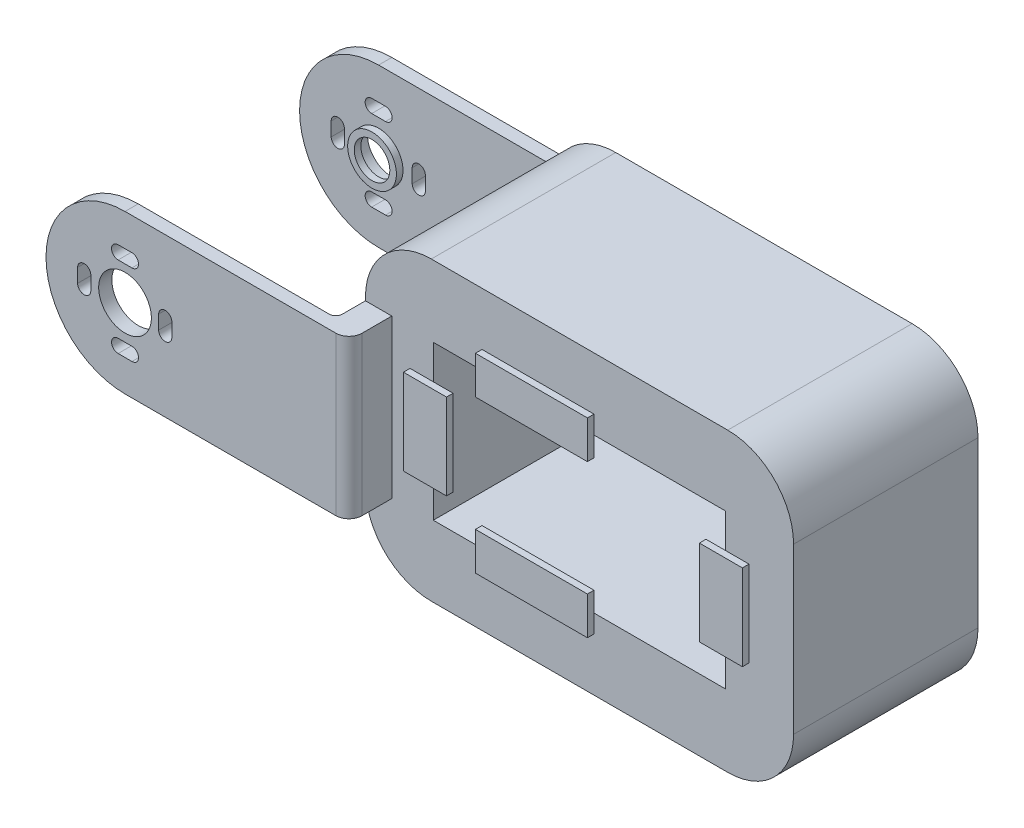
SolidWorks part; units mm, degrees
ref_plane "前基準面" through (0, 0, 0) normal (0, 0, 1) x (1, 0, 0)
ref_plane "上基準面" through (0, 0, 0) normal (0, 1, 0) x (1, 0, 0)
ref_plane "右基準面" through (0, 0, 0) normal (1, 0, 0) x (0, 0, -1)
sketch "草圖1" plane through (0, 0, 0) normal (0, 0, 1) x (1, 0, 0)
  line L0 (-9.02, 0) -> (7.9922, 0) construction
  line L2 (-59.9347, 22.5) -> (5.0653, 22.5)
  line L3 (-59.9347, 22.5) -> (-59.9347, -22.5)
  line L4 (-59.9347, -22.5) -> (5.0653, -22.5)
  line L5 (5.0653, 22.5) -> (5.0653, -22.5)
  dimension "D1" = 45
  dimension "D2" = 22.5
  dimension "D3" = 65
extrude "填料-伸長1" add sketch "草圖1" along normal blind 28
sketch "草圖2" plane through (0, 0, 0) normal (0, 0, 1) x (1, 0, 0)
  line L0 (-59.9347, 0) -> (5.361, 0) construction
  line L1 (-59.9347, 22.5) -> (-59.9347, -22.5) construction
  line L2 (-27.4347, 22.5) -> (-27.4347, -22.5) construction
  line L3 (5.0653, 22.5) -> (-59.9347, 22.5) construction
  line L4 (-59.9347, -22.5) -> (5.0653, -22.5) construction
  line L6 (-49.6347, 11.7) -> (-5.2347, 11.7)
  line L7 (-49.6347, 11.7) -> (-49.6347, -11.7)
  line L8 (-49.6347, -11.7) -> (-5.2347, -11.7)
  line L9 (-5.2347, 11.7) -> (-5.2347, -11.7)
  dimension "D1" = 44.4
  dimension "D2" = 23.4
  dimension "D3" = 10.3
  dimension "D4" = 10.8
extrude "除料-伸長1" cut sketch "草圖2" along normal blind 39
ref_plane "平面1" through (0, 0, 28) normal (0, 0, 1) x (1, 0, 0)
sketch "草圖3" plane through (0, 0, 28) normal (0, 0, 1) x (1, 0, 0)
  line L0 (-59.9347, 22.5) -> (-59.9347, -22.5) construction
  line L2 (-59.9347, 12) -> (-55.9347, 12)
  line L3 (-59.9347, 12) -> (-59.9347, -12)
  line L4 (-59.9347, -12) -> (-55.9347, -12)
  line L5 (-55.9347, 12) -> (-55.9347, -12)
  line L8 (-5.2347, -11.7) -> (-49.6347, -11.7) construction
  dimension "D1" = 4
  dimension "D2" = 24
  dimension "D3" = 0.3
extrude "填料-伸長2" add sketch "草圖3" along normal blind 6
ref_plane "平面2" through (-59.9347, 0, 0) normal (-1, 0, 0) x (0, 0, 1)
sketch "草圖4" plane through (-59.9347, 0, 0) normal (-1, 0, 0) x (0, 0, 1)
  line L0 (34, 12) -> (28, 12) construction
  line L2 (32, 12) -> (34, 12)
  line L3 (32, 12) -> (32, -12)
  line L4 (32, -12) -> (34, -12)
  line L5 (34, 12) -> (34, -12)
  dimension "D1" = 2
ref_plane "平面3" through (0, 0, 33) normal (0, 0, 1) x (1, 0, 0)
sketch "草圖6" plane through (0, 0, 28) normal (0, 0, 1) x (1, 0, 0)
  line L0 (-15.2347, 0.3) -> (5.0653, -22.5)
  line L1 (-5.2347, 11.7) -> (-5.2347, -11.7) construction
  line L2 (-5.2347, -11.7) -> (-49.6347, -11.7) construction
  line L3 (-15.2347, 0.3) -> (-15.2347, -22.5)
  line L4 (-59.9347, -22.5) -> (5.0653, -22.5) construction
  line L5 (-15.2347, -22.5) -> (5.0653, -22.5)
  dimension "D1" = 10
  dimension "D2" = 12
sketch "草圖7" plane through (0, 0, 33) normal (0, 0, 1) x (1, 0, 0)
  line L1 (-59.9347, 12) -> (-59.9347, -12) construction
  line L3 (-59.9347, 0) -> (-109.9347, 0) construction
  line L5 (-96.1347, 1.05) -> (-96.1347, -1.05) construction
  line L6 (-95.1347, 1.05) -> (-95.1347, -1.05)
  line L7 (-97.1347, 1.05) -> (-97.1347, -1.05)
  line L8 (-90.9847, -6.2) -> (-88.8847, -6.2) construction
  line L9 (-90.9847, -5.2) -> (-88.8847, -5.2)
  line L10 (-90.9847, -7.2) -> (-88.8847, -7.2)
  line L11 (-89.9347, 4) -> (-89.9347, -7.9506) construction
  line L12 (-90.9847, 6.1) -> (-88.8847, 6.1) construction
  line L13 (-90.9847, 5.1) -> (-88.8847, 5.1)
  line L14 (-90.9847, 7.1) -> (-88.8847, 7.1)
  line L15 (-83.8347, 1.05) -> (-83.8347, -1.05) construction
  line L16 (-84.8347, 1.05) -> (-84.8347, -1.05)
  line L17 (-82.8347, 1.05) -> (-82.8347, -1.05)
  line L19 (-59.9347, 12) -> (-59.9347, -12)
  line L20 (-59.9347, -12) -> (-89.9347, -12)
  line L21 (-59.9347, 12) -> (-89.9347, 12)
  circle A1 centre (-89.9347, 0) radius 4
  arc A3 (-95.1347, 1.05) -> (-97.1347, 1.05) centre (-96.1347, 1.05) ccw
  arc A4 (-97.1347, -1.05) -> (-95.1347, -1.05) centre (-96.1347, -1.05) ccw
  arc A5 (-90.9847, -5.2) -> (-90.9847, -7.2) centre (-90.9847, -6.2) ccw
  arc A6 (-88.8847, -7.2) -> (-88.8847, -5.2) centre (-88.8847, -6.2) ccw
  arc A7 (-90.9847, 5.1) -> (-90.9847, 7.1) centre (-90.9847, 6.1) cw
  arc A8 (-88.8847, 7.1) -> (-88.8847, 5.1) centre (-88.8847, 6.1) cw
  arc A9 (-84.8347, 1.05) -> (-82.8347, 1.05) centre (-83.8347, 1.05) cw
  arc A10 (-82.8347, -1.05) -> (-84.8347, -1.05) centre (-83.8347, -1.05) cw
  arc A11 (-89.9347, 12) -> (-89.9347, -12) centre (-89.9347, 0) ccw
  point P15 (-96.1347, 0)
  point P20 (-89.9347, -6.2)
  point P31 (-89.9347, 6.1)
  point P38 (-83.8347, 0)
  dimension "D2" = 8
  dimension "D3" = 50
  dimension "D4" = 6.2
  dimension "D6" = 0
  dimension "D12" = 24
  dimension "D5" = 2.1
  dimension "D7" = 2
  dimension "D8" = 2
  dimension "D9" = 0
  dimension "D10" = 2.1
  dimension "D11" = 6.2
  dimension "D13" = 30
extrude "填料-伸長3" add sketch "草圖7" along normal blind 1.5 and the other way blind 0.5
ref_plane "平面4" through (0, 0, 0) normal (0, 0, -1) x (-1, 0, 0)
sketch "草圖8" plane through (0, 0, 0) normal (0, 0, -1) x (-1, 0, 0)
  line L0 (59.9347, 12) -> (59.9347, -12) construction
  line L1 (55.9347, 12) -> (59.9347, 12)
  line L2 (55.9347, 12) -> (55.9347, -12)
  line L3 (55.9347, -12) -> (59.9347, -12)
  line L4 (59.9347, 12) -> (59.9347, -12)
  dimension "D1" = 24
  dimension "D2" = 4
extrude "填料-伸長4" add sketch "草圖8" along normal blind 6 contours L3 L4 L1 L2
fillet "圓角1" radius 10 1 edges at (-59.9347, -22.5, 14) type face fillet first side face at (-59.9347, 0, 13.75) second side face at (-27.4347, -22.5, 14)
fillet "圓角2" radius 10 1 edges at (-59.9347, 22.5, 14) type face fillet first side face at (-27.4347, 22.5, 14) second side face at (-59.9347, 1.6667, 13.75)
fillet "圓角3" radius 10 1 edges at (5.0653, 22.5, 14) type face fillet first side face at (-22.4347, 22.5, 14) second side face at (5.0653, 0, 14)
fillet "圓角4" radius 10 1 edges at (5.0653, -22.5, 14) type face fillet first side face at (-22.4347, -22.5, 14) second side face at (5.0653, -5, 14)
pattern_linear "直線複製排列2" count 2 spacing 38.5 along (0, 0, -1) of "填料-伸長3"
fillet "圓角5" radius 2 1 edges at (-55.9347, 0, -6) type face fillet first side face at (-75.9347, 0, -6) second side face at (-55.9347, 0, -3)
ref_plane "平面5" through (0, 0, -4) normal (0, 0, 1) x (1, 0, 0)
sketch "草圖9" plane through (0, 0, -4) normal (0, 0, 1) x (1, 0, 0)
  circle A0 centre (-89.9347, 0) radius 3.7
  circle A1 centre (-89.9347, 0) radius 2.7
  dimension "D1" = 7.4
  dimension "D2" = 5.4
extrude "填料-伸長5" add sketch "草圖9" along normal blind 1 separate body
ref_plane "平面6" through (0, 0, 29) normal (0, 0, 1) x (1, 0, 0)
sketch "草圖10" plane through (0, 0, 29) normal (0, 0, 1) x (1, 0, 0)
  line L6 (-49.6347, 0) -> (-4.2092, 0) construction
  line L7 (-49.6347, -11.7) -> (-49.6347, 11.7) construction
  line L8 (-27.4347, -11.7) -> (-27.4347, 19.297) construction
  line L9 (-5.2347, -11.7) -> (-49.6347, -11.7) construction
  line L11 (-49.6347, 6.5) -> (-53.1651, 6.5)
  line L14 (-53.1651, 6.5) -> (-53.1651, -6.5)
  line L17 (-49.6347, 6.5) -> (-46.6347, 6.5)
  line L18 (-46.6347, 6.5) -> (-46.6347, -6.5)
  line L20 (-42.2347, -11.7) -> (-42.2347, -8.7)
  line L25 (-42.2347, -11.7) -> (-42.2347, -14.4546)
  line L27 (-8.2347, 6.5) -> (-8.2347, -6.5)
  line L28 (-8.2347, -6.5) -> (-5.2347, -6.5)
  line L29 (-5.2347, -6.5) -> (-1.7043, -6.5)
  line L30 (-1.7043, 6.5) -> (-1.7043, -6.5)
  line L32 (-25.2347, 8.7) -> (-25.2347, 14.4546)
  line L33 (-25.2347, -14.4546) -> (-25.2347, -8.7)
  line L34 (-25.2347, -14.4546) -> (-42.2347, -14.4546)
  line L35 (-25.2347, -8.7) -> (-42.2347, -8.7)
  line L36 (-25.2347, 8.7) -> (-42.2347, 8.7)
  line L37 (-25.2347, 14.4546) -> (-42.2347, 14.4546)
  line L38 (-42.2347, 8.7) -> (-42.2347, 14.4546)
  line L39 (-46.6347, -6.5) -> (-53.1651, -6.5)
  line L40 (-1.7043, 6.5) -> (-8.2347, 6.5)
  dimension "D3" = 13
  dimension "D4" = 6.5
extrude "填料-伸長6" add sketch "草圖10" against normal blind 1 separate body
ref_plane "平面7" through (0, 0, -4) normal (0, 0, -1) x (-1, 0, 0)
sketch "草圖12" plane through (0, 0, -4) normal (0, 0, -1) x (-1, 0, 0)
  circle A0 centre (89.9347, 0) radius 4
  circle A1 centre (89.9347, 0) radius 3.7
extrude "填料-伸長8" add sketch "草圖12" along normal blind 2
ref_plane "平面9" through (0, 0, 34) normal (0, 0, 1) x (1, 0, 0)
sketch "草圖15" plane through (0, 0, 34) normal (0, 0, 1) x (1, 0, 0)
  line L0 (-59.9347, 12) -> (-59.9347, -12) construction
  line L1 (-59.9347, 12) -> (-55.9347, 12)
  line L2 (-59.9347, 12) -> (-59.9347, -12)
  line L3 (-59.9347, -12) -> (-55.9347, -12)
  line L4 (-55.9347, 12) -> (-55.9347, -12)
  line L5 (-55.9347, 12) -> (-59.9347, 12) construction
  dimension "D1" = 24
  dimension "D2" = 4
extrude "填料-伸長10" add sketch "草圖15" along normal blind 0.5
fillet "圓角16" radius 2 1 edges at (-55.9347, 0, 34.5) type face fillet first side face at (-75.9347, 0, 34.5) second side face at (-55.9347, 0, 31.25)
fillet "圓角17" radius 1 1 edges at (-59.9347, 0, 32.5) type face fillet first side face at (-83.8347, 0, 32.5) second side face at (-59.9347, 0, 14.0833)
fillet "圓角18" radius 1 1 edges at (-59.9347, 0, -4) type face fillet first side face at (-59.9347, 0, 13.9167) second side face at (-77.9347, 0, -4)
